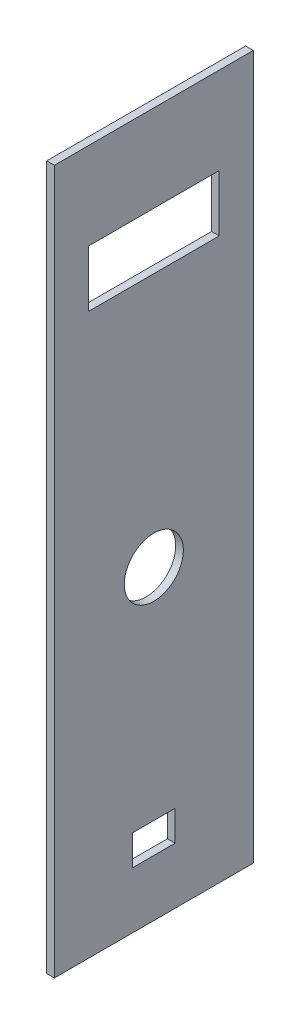
SolidWorks part; units mm, degrees
ref_plane "Front Plane" through (0, 0, 0) normal (0, 0, 1) x (1, 0, 0)
ref_plane "Top Plane" through (0, 0, 0) normal (0, 1, 0) x (1, 0, 0)
ref_plane "Right Plane" through (0, 0, 0) normal (1, 0, 0) x (0, 0, -1)
sketch "Sketch1" plane through (0, 0, 0) normal (1, 0, 0) x (0, 0, -1)
  line L1 (0, 0) -> (82.55, 0)
  line L2 (0, 0) -> (0, 292.1)
  line L3 (0, 292.1) -> (82.55, 292.1)
  line L4 (82.55, 0) -> (82.55, 292.1)
  dimension "D1" = 82.55
  dimension "D2" = 292.1
extrude "Boss-Extrude1" add sketch "Sketch1" along normal blind 3.175 contours L3 L4 L1 L2
sketch "Sketch2" plane through (0, 0, 0) normal (-1, 0, 0) x (0, 0, 1)
  line L0 (0, 292.1) -> (-82.55, 292.1) construction
  line L1 (-66.4, 234.5) -> (-16.15, 234.5)
  line L2 (-66.4, 234.5) -> (-66.4, 254)
  line L3 (-66.4, 254) -> (-16.15, 254)
  line L4 (-16.15, 234.5) -> (-16.15, 254)
  line L5 (0, 292.1) -> (-82.55, 292.1) construction
  point P8 (-41.275, 292.1)
  point P9 (-41.275, 254)
  dimension "D1" = 50.25
  dimension "D2" = 19.5
  dimension "D3" = 38.1
extrude "Cut-Extrude1" cut sketch "Sketch2" against normal up to next
ref_plane "Plane1" through (0, 0, -41.275) normal (0, 0, -1) x (-1, 0, 0)
sketch "Sketch4" plane through (0, 0, 0) normal (-1, 0, 0) x (0, 0, 1)
  line L0 (-41.275, 1.7463) -> (-41.275, -1.7462) construction
  line L2 (0, 0) -> (-82.55, 0) construction
  circle A0 centre (-41.275, 127) radius 10.25
  dimension "D1" = 20.5
  dimension "D2" = 127
extrude "Cut-Extrude2" cut sketch "Sketch4" against normal up to next
sketch "Sketch5" plane through (0, 0, 0) normal (-1, 0, 0) x (0, 0, 1)
  line L0 (-41.275, 1.7463) -> (-41.275, -1.7462) construction
  line L1 (-48.125, 33.95) -> (-34.425, 33.95)
  line L2 (-48.125, 33.95) -> (-48.125, 25.4)
  line L3 (-48.125, 25.4) -> (-34.425, 25.4)
  line L4 (-34.425, 33.95) -> (-34.425, 25.4)
  line L5 (0, 0) -> (-82.55, 0) construction
  point P4 (-41.275, 33.95)
  dimension "D1" = 8.55
  dimension "D2" = 13.7
  dimension "D3" = 25.4
extrude "Cut-Extrude3" cut sketch "Sketch5" against normal up to next
sketch "Sketch6" plane through (0, 0, 0) normal (-1, 0, 0) x (0, 0, 1)
  line L4 (-16.15, 254) -> (-66.4, 254) construction
  line L5 (-16.15, 234.5) -> (-16.15, 254) construction
  line L7 (-66.4, 234.5) -> (-16.15, 234.5) construction
  line L10 (-66.4, 254) -> (-66.4, 234.5) construction
  line L30 (-34.425, 25.4) -> (-34.425, 33.95) construction
  line L35 (-48.125, 25.4) -> (-34.425, 25.4) construction
  line L41 (-48.125, 33.95) -> (-48.125, 25.4) construction
  line L48 (-34.425, 33.95) -> (-48.125, 33.95) construction
  line L64 (-48.125, 33.95) -> (-48.125, 25.4)
  line L65 (-48.125, 25.4) -> (-34.425, 25.4)
  line L66 (-34.425, 25.4) -> (-34.425, 33.95)
  line L67 (-34.425, 33.95) -> (-48.125, 33.95)
  line L68 (-66.4, 254) -> (-66.4, 234.5)
  line L69 (-66.4, 234.5) -> (-16.15, 234.5)
  line L70 (-16.15, 234.5) -> (-16.15, 254)
  line L71 (-16.15, 254) -> (-66.4, 254)
  line L72 (-14.15, 256) -> (-68.4, 256)
  line L73 (-68.4, 256) -> (-68.4, 232.5)
  line L74 (-68.4, 232.5) -> (-14.15, 232.5)
  line L75 (-14.15, 232.5) -> (-14.15, 256)
  line L76 (-32.425, 35.95) -> (-50.125, 35.95)
  line L77 (-50.125, 35.95) -> (-50.125, 23.4)
  line L78 (-50.125, 23.4) -> (-32.425, 23.4)
  line L79 (-32.425, 23.4) -> (-32.425, 35.95)
  circle A0 centre (-41.275, 127) radius 10.25 construction
  circle A8 centre (-41.275, 127) radius 10.25
  circle A9 centre (-41.275, 127) radius 12.25
  dimension "D1" = 2
extrude "Cut-Extrude4" cut sketch "Sketch6" against normal up to next
